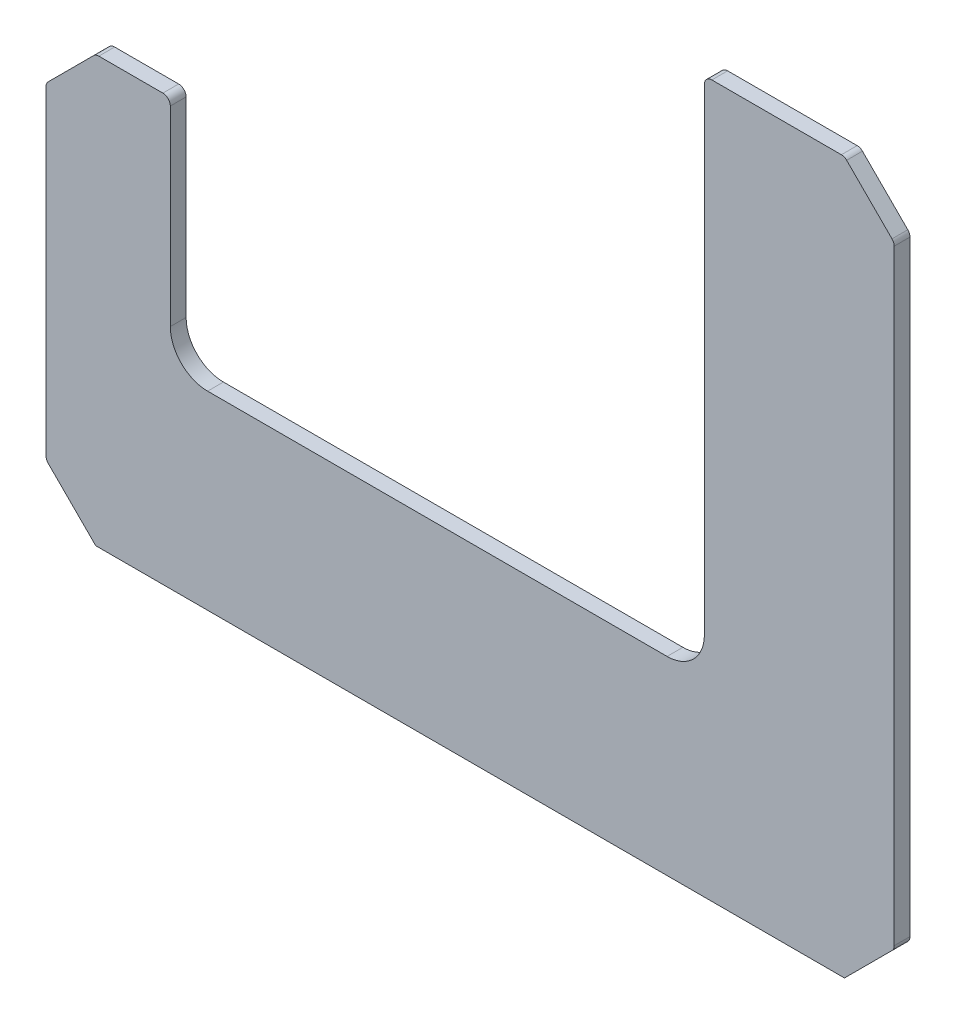
SolidWorks part; units mm, degrees
material "Teak"
ref_plane "Front Plane" through (0, 0, 0) normal (0, 0, 1) x (1, 0, 0)
ref_plane "Top Plane" through (0, 0, 0) normal (0, 1, 0) x (1, 0, 0)
ref_plane "Right Plane" through (0, 0, 0) normal (1, 0, 0) x (0, 0, -1)
sketch "Sketch2" plane through (0, 0, 0) normal (0, 0, 1) x (1, 0, 0)
  line L0 (-157.4125, 94.825) -> (-107.4125, 94.825)
  line L1 (-107.4125, 94.825) -> (-107.4125, 0)
  line L2 (-107.4125, 0) -> (107.4125, 0)
  line L3 (107.4125, 0) -> (107.4125, 209.825)
  line L4 (107.4125, 209.825) -> (183.7625, 209.825)
  line L5 (183.7625, 209.825) -> (183.7625, -76.35)
  line L6 (183.7625, -76.35) -> (58.275, -76.35)
  line L7 (-31.925, -76.35) -> (58.275, -76.35)
  line L10 (-31.925, -76.35) -> (-157.4125, -76.35)
  line L11 (-157.4125, -76.35) -> (-157.4125, 94.825)
  line L12 (-37.4125, 0) -> (-37.4125, 144.825) construction
  point P10 (-37.4125, 0)
  point P14 (107.4125, 144.825)
  point P15 (-37.4125, 94.825)
  dimension "D1" = 144.825
  dimension "D2" = 144.825
  dimension "D6" = 90.2
  dimension "D7" = 76.35
  dimension "D10" = 50
  dimension "D11" = 50
extrude "Boss-Extrude1" add sketch "Sketch2" along normal blind 3.175 and the other way blind 3.175
chamfer "Chamfer1" distance 20 angle 45 4 edges at (-157.4125, -76.35, 0) (183.7625, -76.35, 0) (183.7625, 209.825, 0) (-157.4125, 94.825, 0)
fillet "Fillet1" radius 15 2 edges at (107.4125, 0, 0) (-107.4125, 0, 0)
fillet "Fillet2" radius 3 8 edges at (183.7625, -56.35, 0) (-157.4125, -56.35, 0) (-157.4125, 74.825, 0) (-137.4125, 94.825, 0) (-107.4125, 94.825, 0) (183.7625, 189.825, 0) (163.7625, 209.825, 0) (107.4125, 209.825, 0)
sketch "Sketch3" plane through (0, 0, 3.175) normal (0, 0, 1) x (1, 0, 0)
  line L0 (-94.6381, 69.9757) -> (-94.6381, 14.7992)
  line L1 (-94.6381, 14.7992) -> (-97.8131, 14.7992)
  line L2 (-97.8131, 14.7992) -> (-97.8131, 69.9757)
  line L3 (-97.8131, 69.9757) -> (-94.6381, 69.9757)
  line L4 (-127.4635, 65.4691) -> (-114.3536, 78.579)
  line L5 (-114.3536, 78.579) -> (-112.1085, 76.3339)
  line L6 (-112.1085, 76.3339) -> (-125.2184, 63.2241)
  line L7 (-125.2184, 63.2241) -> (-127.4635, 65.4691)
  line L8 (-129.3392, 54.7846) -> (-126.1642, 54.7846)
  line L9 (-126.1642, 54.7846) -> (-126.1642, -28.3138)
  line L10 (-126.1642, -28.3138) -> (-129.3392, -28.3138)
  line L11 (-129.3392, -28.3138) -> (-129.3392, 54.7846)
  line L12 (-127.4635, -37.1329) -> (-125.2184, -34.8879)
  line L13 (-125.2184, -34.8879) -> (-110.9382, -49.1681)
  line L14 (-110.9382, -49.1681) -> (-113.1832, -51.4132)
  line L15 (-113.1832, -51.4132) -> (-127.4635, -37.1329)
  line L16 (-67.7784, -44.3183) -> (-67.7784, -41.1433)
  line L17 (-67.7784, -41.1433) -> (53.0181, -41.1433)
  line L18 (53.0181, -41.1433) -> (53.0181, -44.3183)
  line L19 (53.0181, -44.3183) -> (-67.7784, -44.3183)
  line L20 (114.9313, -49.5303) -> (117.1763, -51.7753)
  line L21 (117.1763, -51.7753) -> (131.7883, -37.1634)
  line L22 (131.7883, -37.1634) -> (129.5432, -34.9183)
  line L23 (129.5432, -34.9183) -> (114.9313, -49.5303)
  line L24 (-67.7784, -4.1746) -> (-67.7784, -7.3496)
  line L25 (-67.7784, -7.3496) -> (63.5847, -7.3496)
  line L26 (63.5847, -7.3496) -> (63.5847, -4.1746)
  line L27 (63.5847, -4.1746) -> (-67.7784, -4.1746)
  line L28 (92.7516, 20.9162) -> (91.2159, 151.9937)
  line L29 (91.2159, 151.9937) -> (94.3909, 151.9937)
  line L30 (94.3909, 151.9937) -> (95.9266, 20.9162)
  line L31 (95.9266, 20.9162) -> (92.7516, 20.9162)
  line L32 (96.8341, 161.8762) -> (96.8341, 158.7012)
  line L33 (96.8341, 158.7012) -> (112.5649, 158.7012)
  line L34 (112.5649, 158.7012) -> (112.5649, 161.8762)
  line L35 (112.5649, 161.8762) -> (96.8341, 161.8762)
  line L37 (117.7781, 156.4535) -> (120.0231, 158.6985)
  line L38 (120.0231, 158.6985) -> (133.8694, 144.8523)
  line L39 (133.8694, 144.8523) -> (131.6243, 142.6072)
  line L40 (131.6243, 142.6072) -> (117.7781, 156.4535)
  line L41 (129.9213, 134.1701) -> (133.0963, 134.1701)
  line L42 (133.0963, 134.1701) -> (133.0963, -24.961)
  line L43 (133.0963, -24.961) -> (129.9213, -24.961)
  line L44 (129.9213, -24.961) -> (129.9213, 134.1701)
  line L45 (163.7625, -76.35) -> (182.8838, -57.2287) construction
  line L46 (-156.5338, -57.2287) -> (-137.4125, -76.35) construction
  line L47 (-138.2912, 93.9463) -> (-156.5338, 75.7037) construction
  line L48 (182.8838, 190.7037) -> (164.6412, 208.9463) construction
  dimension "D1" = 3.175
extrude "Cut-Extrude1" [suppressed] cut sketch "Sketch3" against normal through all
sketch "magnets" plane through (0, 0, 3.175) normal (0, 0, 1) x (1, 0, 0)
  point P0 (94.6751, 158.4052)
  point P1 (114.7572, -50)
  point P2 (131.9288, 140.6094)
  point P3 (131.9288, -32.8111)
  point P4 (0, -44.1618)
  point P5 (-114.0039, -50)
  point P6 (-130.8821, -32.8111)
  point P9 (-130.8821, 62.3605)
  point P10 (-93.5499, 79.7316)
  point P12 (0, -4.7392)
equation "\"dX\"= 148mm - \"t_wood\" / 2"
equation "\"dY\"= 148mm - \"t_wood\" / 2"
equation "\"hmotor\"= 70mm"
equation "\"D1@Sketch2\"=\"dY\""
equation "\"D2@Sketch2\"=\"dX\""
equation "\"D5@Sketch2\"=\"hmotor\"+\"t_wood\""
equation "\"D6@Sketch2\"=\"hmotor\"+\"d_floor\"+\"t_wood\"*2"
equation "\"t_wood\"= 0.25in"
equation "\"D1@Boss-Extrude1\"=\"t_wood\"/2"
equation "\"D2@Boss-Extrude1\"=\"t_wood\"/2"
equation "\"D1@Sketch3\"=\"t_wood\"/2"
equation "\"d_floor\"= 7.50mm"
equation "\"D7@Sketch2\"=\"hmotor\" + \"t_wood\""
equation "\"D1@Sketch4\"=\"t_wood\" / 2"
